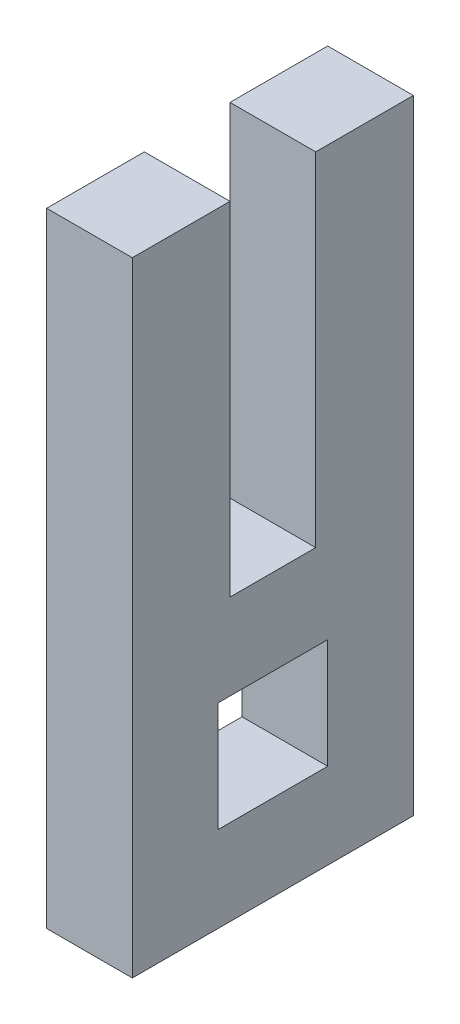
SolidWorks part; units mm, degrees
material "Balsa"
ref_plane "Front Plane" through (0, 0, 0) normal (0, 0, 1) x (1, 0, 0)
ref_plane "Top Plane" through (0, 0, 0) normal (0, 1, 0) x (1, 0, 0)
ref_plane "Right Plane" through (0, 0, 0) normal (1, 0, 0) x (0, 0, -1)
sketch "Sketch2" plane through (0, 0, 0) normal (1, 0, 0) x (0, 0, -1)
  line L0 (0, 0) -> (0, 46.228)
  line L1 (0, 46.228) -> (7.239, 46.228)
  line L2 (7.239, 46.228) -> (7.239, 20.828)
  line L3 (7.239, 20.828) -> (13.589, 20.828)
  line L4 (13.589, 20.828) -> (13.589, 46.228)
  line L5 (13.589, 46.228) -> (20.828, 46.228)
  line L6 (20.828, 46.228) -> (20.828, 0)
  line L7 (20.828, 0) -> (0, 0)
  line L9 (6.35, 6.35) -> (14.478, 6.35)
  line L10 (6.35, 6.35) -> (6.35, 14.478)
  line L11 (6.35, 14.478) -> (14.478, 14.478)
  line L12 (14.478, 6.35) -> (14.478, 14.478)
  point P13 (10.414, 20.828)
  point P14 (10.414, 20.828)
  point P15 (8.2028, 20.828)
  point P16 (10.414, 0)
  dimension "D1" = 6.35
  dimension "D2" = 8.128
  dimension "D3" = 8.128
  dimension "D4" = 6.35
  dimension "D5" = 6.35
  dimension "D6" = 6.35
  dimension "D7" = 6.35
  dimension "D8" = 25.4
extrude "Boss-Extrude1" add sketch "Sketch2" along normal blind 6.35
equation "\"D4@Sketch2\"=\"D5@Sketch2\""
equation "\"D6@Sketch2\"=\"D5@Sketch2\""
